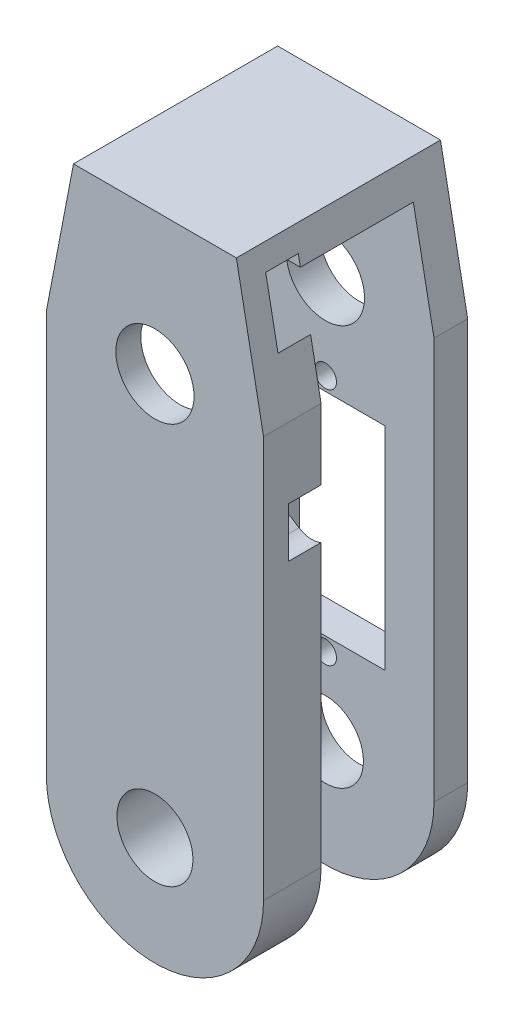
SolidWorks part; units mm, degrees
note: The reader was unsure of these and kept them because the rebuilt part matched: shared geometry of "Sketch1<5>", "Sketch4<3>".
ref_plane "Front Plane" through (0, 0, 0) normal (0, 0, 1) x (1, 0, 0)
ref_plane "Top Plane" through (0, 0, 0) normal (0, 1, 0) x (1, 0, 0)
ref_plane "Right Plane" through (0, 0, 0) normal (1, 0, 0) x (0, 0, -1)
sketch "Sketch1"
  line L0 (0, -11.7475) -> (0, -10.16) construction
  line L9 (-12.7, 0) -> (-9.525, 16.51)
  line L11 (12.7, -46.99) -> (12.7, 0)
  line L13 (-12.7, -46.99) -> (-12.7, 0)
  line L14 (-9.525, 16.51) -> (9.525, 16.51)
  line L15 (9.525, 16.51) -> (12.7, 0)
  line L16 (0, 16.51) -> (0, 0) construction
  line L17 (-6.985, -36.5125) -> (6.985, -36.5125)
  line L18 (-6.985, -36.5125) -> (-6.985, -11.7475)
  line L19 (-6.985, -11.7475) -> (6.985, -11.7475)
  line L20 (6.985, -36.5125) -> (6.985, -11.7475)
  line L21 (0, -38.1) -> (0, -10.16) construction
  line L22 (0, -24.13) -> (6.985, -24.13) construction
  circle A0 centre (0, 0) radius 4.572
  arc A1 (-12.7, -46.99) -> (12.7, -46.99) centre (0, -46.99) ccw
  circle A2 centre (0, -10.16) radius 1.2954
  circle A3 centre (0, -38.1) radius 1.2954
  circle A4 centre (0, -46.99) radius 4.445
  dimension "D1" = 9.144
  dimension "D5" = 76.2
  dimension "D3" = 2.5908
  dimension "D8" = 8.89
  dimension "D2" = 27.94
  dimension "D4" = 19.05
  dimension "D6" = 25.4
  dimension "D7" = 10.16
  dimension ".65" = 16.51
  dimension "D9" = 13.97
  dimension "D10" = 24.765
sketch "Sketch1<5>" plane through (0, 0, 0) normal (0, 0, 1) x (1, 0, 0) same geometry as "Sketch1"
extrude "Boss-Extrude1" add sketch "Sketch1" along normal blind 6.731
extrude "Boss-Extrude3" add sketch "Sketch1<5>" against normal blind 3.937 from offset 13.208 separate body contours L17 L20 L19 L18 | A2 | L13 A1 L11 L15 L14 L9 A4 A3 A2 L20 L17 L18 L19 A0 | A3 offset against normal yes
sketch "Sketch4" plane through (0, 0, 0) normal (0, 0, -1) x (-1, 0, 0)
  line L0 (-13.0815, -13.0815) -> (13.0815, 13.0815) construction
  line L6 (-13.0815, 13.0815) -> (13.0815, -13.0815) construction
  line L7 (7.57, 1.4889) -> (13.3608, 10.4574) construction
  line L8 (1.4889, 7.57) -> (10.4574, 13.3608) construction
  line L16 (7.57, 1.4889) -> (1.4889, 7.57) construction
  line L17 (13.3608, -10.4574) -> (7.57, -1.4889) construction
  line L18 (10.4574, -13.3608) -> (1.4889, -7.57) construction
  line L19 (-13.3608, -10.4574) -> (-7.57, -1.4889) construction
  line L20 (-10.4574, -13.3608) -> (-1.4889, -7.57) construction
  line L21 (-10.4574, 13.3608) -> (-1.4889, 7.57) construction
  line L22 (-7.57, 1.4889) -> (-13.3608, 10.4574) construction
  line L23 (8.0238, 1.0211) -> (13.8942, 10.113)
  line L24 (1.0211, 8.0238) -> (10.113, 13.8942)
  line L25 (-10.113, 13.8942) -> (-1.0211, 8.0238)
  line L26 (-8.0238, 1.0211) -> (-13.8942, 10.113)
  line L27 (-13.8942, -10.113) -> (-8.0238, -1.0211)
  line L28 (-10.113, -13.8942) -> (-1.0211, -8.0238)
  line L29 (10.113, -13.8942) -> (1.0211, -8.0238)
  line L30 (13.8942, -10.113) -> (8.0238, -1.0211)
  line L36 (12.7, -46.99) -> (12.7, 0)
  line L37 (12.7, 0) -> (9.525, 16.51)
  line L38 (9.525, 16.51) -> (-9.525, 16.51)
  line L39 (-9.525, 16.51) -> (-12.7, 0)
  line L40 (-12.7, 0) -> (-12.7, -46.99)
  line L41 (12.7, -46.99) -> (12.7, 0)
  line L42 (12.7, 0) -> (9.525, 16.51)
  line L43 (9.525, 16.51) -> (-9.525, 16.51)
  line L44 (-9.525, 16.51) -> (-12.7, 0)
  line L45 (-12.7, 0) -> (-12.7, -46.99)
  circle A0 centre (0, 0) radius 6.7736 construction
  arc A1 (10.4574, 13.3608) -> (13.3608, 10.4574) centre (11.5966, 11.5966) cw construction
  arc A2 (-1.4889, 7.57) -> (1.4889, 7.57) centre (0, 8.5636) ccw construction
  arc A3 (7.57, 1.4889) -> (7.57, -1.4889) centre (8.5636, 0) ccw construction
  arc A4 (-1.4889, -7.57) -> (1.4889, -7.57) centre (0, -8.5636) cw construction
  arc A5 (13.3608, -10.4574) -> (10.4574, -13.3608) centre (11.5966, -11.5966) cw construction
  arc A6 (-7.57, 1.4889) -> (-7.57, -1.4889) centre (-8.5636, 0) cw construction
  arc A7 (-13.3608, -10.4574) -> (-10.4574, -13.3608) centre (-11.5966, -11.5966) ccw construction
  arc A8 (-13.3608, 10.4574) -> (-10.4574, 13.3608) centre (-11.5966, 11.5966) cw construction
  circle A9 centre (0, 0) radius 1.7
  arc A26 (10.113, 13.8942) -> (13.8942, 10.113) centre (11.5966, 11.5966) cw
  arc A27 (-1.0211, 8.0238) -> (1.0211, 8.0238) centre (0, 8.5636) ccw
  arc A28 (-13.8942, 10.113) -> (-10.113, 13.8942) centre (-11.5966, 11.5966) cw
  arc A29 (-8.0238, 1.0211) -> (-8.0238, -1.0211) centre (-8.5636, 0) cw
  arc A30 (-13.8942, -10.113) -> (-10.113, -13.8942) centre (-11.5966, -11.5966) ccw
  arc A31 (-1.0211, -8.0238) -> (1.0211, -8.0238) centre (0, -8.5636) cw
  arc A32 (13.8942, -10.113) -> (10.113, -13.8942) centre (11.5966, -11.5966) cw
  arc A33 (8.0238, 1.0211) -> (8.0238, -1.0211) centre (8.5636, 0) ccw
  arc A35 (-12.7, -46.99) -> (12.7, -46.99) centre (0, -46.99) ccw
  arc A36 (-12.7, -46.99) -> (12.7, -46.99) centre (0, -46.99) ccw
  point P5 (0, 0)
  point P8 (0, 0)
  point P32 (4.5294, 4.5294)
  point P67 (0, 0)
  line M6 (12.7, -46.99) -> (12.7, 0)
  line M7 (12.7, 0) -> (9.525, 16.51)
  dimension "D2" = 2.1
  dimension "D3" = 1.79
  dimension "D6" = 3.4
  dimension "D1" = 18.5
  dimension "D4" = 7.57
  dimension "D5" = 8.6
  dimension "D7" = 0.635
  dimension "D8" = 0
extrude "Cut-Extrude4" cut sketch "Sketch4" against normal blind 3.81
sketch "Sketch5" plane through (0, 0, 0) normal (0, 0, -1) x (-1, 0, 0)
  line L0 (-9.525, 16.51) -> (9.525, 16.51)
  line L1 (9.525, 16.51) -> (10.2821, 12.573)
  line L2 (9.525, 16.51) -> (12.7, 0) construction
  line L3 (10.2821, 12.573) -> (-10.2821, 12.573)
  line L4 (-12.7, 0) -> (-9.525, 16.51) construction
  line L5 (-10.2821, 12.573) -> (-9.525, 16.51)
  dimension "D1" = 3.937
extrude "Boss-Extrude5" add sketch "Sketch5" along normal blind 16.4211
extrude "Boss-Extrude6" add sketch "Sketch4<3>" against normal blind 4.572 contours L23 A33 L30 M6 M7
sketch "Sketch4<3>" plane through (0, 0, 0) normal (0, 0, -1) x (-1, 0, 0) same geometry as "Sketch4"
